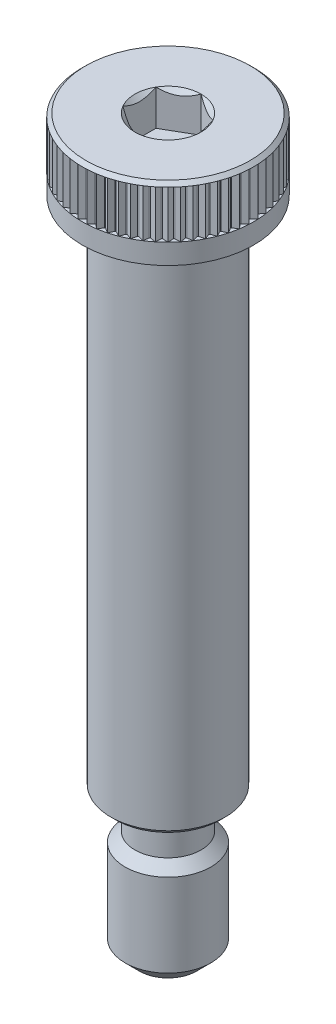
SolidWorks part; units mm, degrees
ref_plane "Front" through (0, 0, 0) normal (0, 0, 1) x (1, 0, 0)
ref_plane "Top" through (0, 0, 0) normal (0, 1, 0) x (1, 0, 0)
ref_plane "Right" through (0, 0, 0) normal (1, 0, 0) x (0, 0, -1)
sketch "Sketch1" plane through (0, 0, 0) normal (0, 1, 0) x (1, 0, 0)
  circle A0 centre (0, 0) radius 9.525
  point P3 (0, -9.525)
  dimension "Head Dia" = 19.05
extrude "Extrude1" add sketch "Sketch1" along normal blind 7.9375
sketch "Sketch2" plane through (0, 7.9375, 0) normal (0, 1, 0) x (-1, 0, 0)
  line L1 (0, -3.6662) -> (3.175, -1.8331)
  line L2 (3.175, -1.8331) -> (3.175, 1.8331)
  line L3 (3.175, 1.8331) -> (0, 3.6662)
  line L4 (0, 3.6662) -> (-3.175, 1.8331)
  line L5 (-3.175, 1.8331) -> (-3.175, -1.8331)
  line L6 (-3.175, -1.8331) -> (0, -3.6662)
  circle A0 centre (0, 0) radius 3.175 construction
  circle A1 centre (0, 0) radius 9.525 construction
  dimension "Hex Key" = 6.35
extrude "Cut-Extrude1" cut sketch "Sketch2" against normal blind 3.9688
sketch "Sketch18" plane through (0, 7.9375, 0) normal (0, 1, 0) x (1, 0, 0)
  circle A0 centre (0, 0) radius 3.6662
extrude "Cut-Extrude4" cut sketch "Sketch18" against normal blind 1.3229 draft 45
ref_plane "Plane2" through (0, -57.15, 0) normal (0, -1, 0) x (1, 0, 0)
sketch "Sketch4" plane through (0, -57.15, 0) normal (0, -1, 0) x (1, 0, 0)
  circle A0 centre (0, 0) radius 6.35
  circle A1 centre (0, 0) radius 9.525 construction
  dimension "Shoulder Dia" = 12.7
extrude "Extrude2" add sketch "Sketch4" against normal blind 57.15
sketch "Sketch5" plane through (0, -57.15, 0) normal (0, -1, 0) x (1, 0, 0)
  circle A0 centre (0, 0) radius 4.7625
  circle A2 centre (0, 0) radius 6.35 construction
  dimension "Thread Dia" = 9.525
extrude "Extrude3" add sketch "Sketch5" along normal blind 15.875
sketch "Sketch16" plane through (0, 0, 0) normal (1, 0, 0) x (0, 0, -1)
  line L0 (-4.7625, -73.025) -> (4.7625, -73.025) construction
  line L2 (-4.7625, -57.15) -> (-4.7625, -73.025) construction
  point P0 (-4.7625, -67.0719)
  dimension "D1" = 5.9531
chamfer "Chamfer1" distance 1.5875 angle 45 1 edges at (0, -73.025, -4.7625)
sketch "Sketch12" plane through (0, -73.025, 0) normal (0, -1, 0) x (1, 0, 0)
  circle A0 centre (0, 0) radius 4.7625
  circle A1 centre (0, 0) radius 4.7625 construction
curve "Helix/Spiral1" pitch 1.5875 height 15.0812 turns 9.5 parameters "Thread Pitch "=1.5875
sketch "Sketch13" plane through (0, 0, 0) normal (0, 0, 1) x (1, 0, 0)
  line L0 (4.7625, -73.025) -> (4.7625, -74.4141)
  line L1 (4.7625, -74.4141) -> (3.7314, -73.8188)
  line L2 (3.7314, -73.8188) -> (3.7314, -73.6203)
  line L3 (3.7314, -73.6203) -> (4.7625, -73.025)
  line L4 (4.7625, -73.7195) -> (3.7314, -73.7195) construction
  line L6 (4.2469, -73.3227) -> (4.2469, -74.1164) construction
  line L7 (-3.175, -73.025) -> (3.175, -73.025) construction
  line L8 (4.7625, -71.4375) -> (4.7625, -57.15) construction
  dimension "D1" = 60
  dimension "D2" = 0.1984
  dimension "D3" = 0.7937
sweep "Cut-Sweep1" [suppressed] cut profiles "Sketch13" path "Helix/Spiral1"
sketch "Sketch17" plane through (0, 0, 0) normal (0, 0, 1) x (1, 0, 0)
  line L0 (-6.35, -57.15) -> (6.35, -57.15) construction
  line L1 (0, 0) -> (0, -57.15) construction
  line L2 (4.8628, -57.15) -> (6.35, -57.15)
  line L3 (6.35, -61.1187) -> (6.35, -57.15)
  line L4 (6.35, -57.15) -> (0, -57.15) construction
  line L5 (3.6722, -58.3406) -> (3.6722, -61.1187)
  line L6 (3.6722, -61.1187) -> (6.35, -61.1187) construction
  line L7 (3.6722, -61.1187) -> (6.35, -63.7966)
  line L8 (6.35, -63.7966) -> (6.35, -61.1187)
  line L9 (3.7314, -73.8188) -> (3.7314, -73.6203) construction
  arc A0 (4.8628, -57.15) -> (3.6722, -58.3406) centre (4.8628, -58.3406) ccw
  point P14 (3.6722, -57.15)
revolve "Cut-Revolve1" cut sketch "Sketch17" angle 360 about L1
chamfer "Chamfer2" distance 0.5292 angle 45 1 edges at (0, -57.15, -6.35)
ref_plane "Plane1" through (0, 7.5406, 0) normal (0, 1, 0) x (-1, 0, 0)
sketch "Sketch10" plane through (0, 7.5406, 0) normal (0, 1, 0) x (-1, 0, 0)
  line L0 (0, 0) -> (-9.0495, 0) construction
  line L1 (0, 0) -> (-9.5119, -0.4985) construction
  line L2 (-9.5119, -0.4985) -> (-9.6514, -0.5058)
  line L3 (-9.5119, -0.4985) -> (-9.075, -0.0616)
  line L4 (0, 0) -> (-9.5119, 0.4985) construction
  line L5 (-9.075, 0.0616) -> (-9.5119, 0.4985)
  line L6 (-9.6514, -0.5058) -> (-9.6514, 0.5058)
  line L7 (-9.6514, 0.5058) -> (-9.5119, 0.4985)
  circle A0 centre (0, 0) radius 9.525 construction
  arc A2 (-9.075, -0.0616) -> (-9.075, 0.0616) centre (-9.1366, 0) ccw
  point P3 (-9.525, 0)
  dimension "D4" = 0.0871
  dimension "D1" = 90
  dimension "D2" = 6
  dimension "D3" = 0.1395
extrude "Cut-Extrude3" cut sketch "Sketch10" against normal blind 5.2917
pattern_circular "CirPattern2" count 60 over 360 about axis through (0, 0, 0) along (0, -1, 0) of "Cut-Extrude3"
chamfer "Chamfer3" distance 0.3969 angle 45 1 edges at (0, 7.9375, 9.525)
sketch "Sketch14" plane through (0, 7.9375, 0) normal (0, 1, 0) x (1, 0, 0)
  circle A0 centre (0, 0) radius 9.525
  arc A1 (-5.9943, -7.4023) -> (-5.1877, -7.9883) centre (0, 0) ccw construction
sketch "Sketch15" plane through (0, 0, 0) normal (1, 0, 0) x (0, 0, -1)
  line L0 (-4.7625, 0) -> (-4.7625, -73.025)
  line L1 (4.7625, -73.025) -> (4.7625, 0)
equation "\"D1@Cut-Extrude1\"=\"Head Ht@Extrude1\"/2"
equation "\"D1@Cut-Extrude3\"=\"Head Ht@Extrude1\"*2/3"
equation "\"D1@Chamfer1\" = \"Thread Length@Extrude3\" * .1"
equation "\"D3@Helix/Spiral1\" = \"Thread Length@Extrude3\" -  ( \"Thread Pitch @Helix/Spiral1\" * .5 ) "
equation "\"D2@Sketch13\" = \"Thread Pitch @Helix/Spiral1\" * .125"
equation "\"D3@Sketch13\" = \"Thread Pitch @Helix/Spiral1\" * .5"
equation "\"D3@Sketch10\" = \"Head Dia@Sketch1\" * .0073205143"
equation "\"D4@Sketch10\" = \"Head Dia@Sketch1\" * .0045714286"
equation "\"D1@Sketch16\" = \"Thread Pitch @Helix/Spiral1\"*3.750"
equation "\"D1@Chamfer2\" = \"Thread Pitch @Helix/Spiral1\"/3"
equation "\"D1@Plane1\" = \"Head Ht@Extrude1\"/20"
equation "\"D1@Chamfer3\" = \"Head Ht@Extrude1\"/20"
equation "\"D1@Cut-Extrude4\" = \"D1@Cut-Extrude1\"/3"
equation "\"Thread Neck Width@Sketch17\" = \"Thread Length@Extrude3\" * .25"
equation "\"Thread Neck Fillet@Sketch17\" = \"Thread Neck Width@Sketch17\" * .3"
